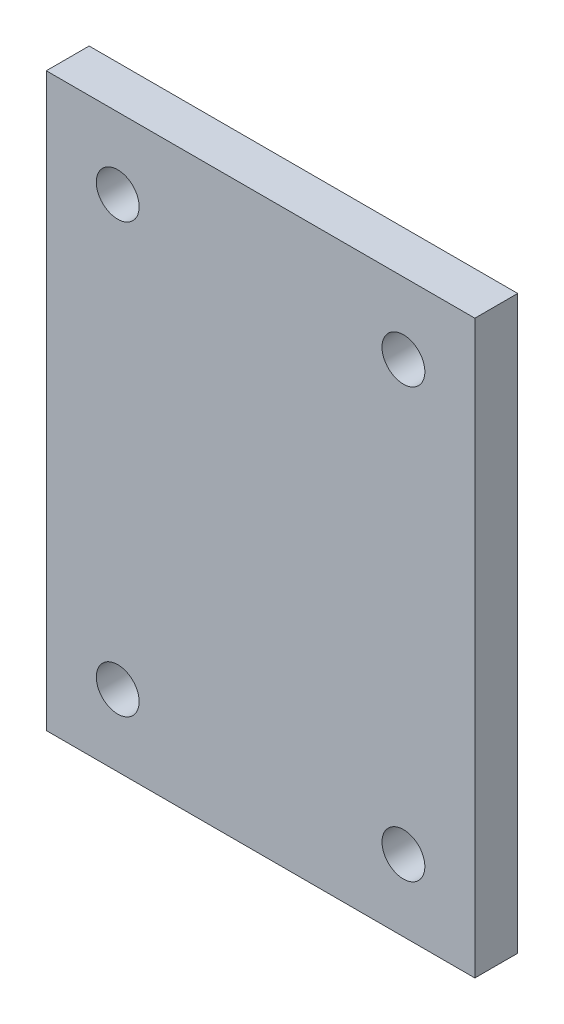
SolidWorks part; units mm, degrees
ref_plane "Plan de face" through (0, 0, 0) normal (0, 0, 1) x (1, 0, 0)
ref_plane "Plan de dessus" through (0, 0, 0) normal (0, 1, 0) x (1, 0, 0)
ref_plane "Plan de droite" through (0, 0, 0) normal (1, 0, 0) x (0, 0, -1)
sketch "Esquisse1" plane through (0, 0, 0) normal (0, 0, 1) x (1, 0, 0)
  line L0 (0, 20) -> (0, -20) construction
  line L1 (-15, -20) -> (15, -20)
  line L2 (-15, -20) -> (-15, 20)
  line L3 (-15, 20) -> (15, 20)
  line L4 (15, -20) -> (15, 20)
  line L5 (-15, -20) -> (15, 20) construction
  line L6 (-15, 20) -> (15, -20) construction
  line L8 (15, 0) -> (-15, 0) construction
  circle A0 centre (-10, 15) radius 1.5
  circle A1 centre (10, 15) radius 1.5
  circle A2 centre (10, -15) radius 1.5
  circle A3 centre (-10, -15) radius 1.5
  point P0 (0, 0)
  dimension "D4" = 10
  dimension "D5" = 3
  dimension "D1" = 40
  dimension "D2" = 30
  dimension "D3" = 15
extrude "Boss.-Extru.1" add sketch "Esquisse1" along normal blind 3
